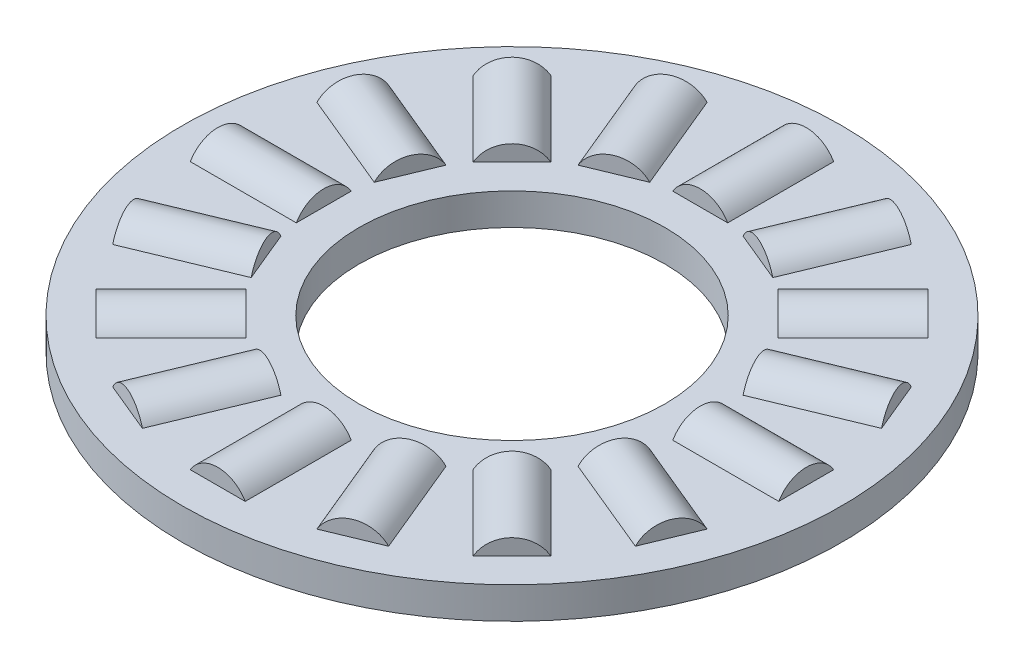
SolidWorks part; units mm, degrees
material "Alloy Steel"
ref_plane "Front Plane" through (0, 0, 0) normal (0, 0, 1) x (1, 0, 0)
ref_plane "Top Plane" through (0, 0, 0) normal (0, 1, 0) x (1, 0, 0)
ref_plane "Right Plane" through (0, 0, 0) normal (1, 0, 0) x (0, 0, -1)
sketch "Sketch1" plane through (0, 0, 0) normal (1, 0, 0) x (0, 0, -1)
  line L0 (-10.3187, 0) -> (10.3188, 0) construction
  line L1 (0, -0.9922) -> (0, 0.9922) construction
  line L2 (-10.3187, 0.4961) -> (-4.7879, 0.4961)
  line L3 (-10.3187, 0.4961) -> (-10.3187, -0.4961)
  line L4 (-10.3187, -0.4961) -> (-4.7879, -0.4961)
  line L5 (-4.7879, 0.4961) -> (-4.7879, -0.4961)
  line L7 (-7.5533, 0.9922) -> (-7.5533, 0.4961) construction
  line L8 (-9.2126, 0.9922) -> (-5.8941, 0.9922) construction
  line L9 (-9.2126, 0.9922) -> (-9.2126, -0.9922) construction
  line L10 (-9.2126, -0.9922) -> (-5.8941, -0.9922) construction
  line L11 (-5.8941, 0.9922) -> (-5.8941, -0.9922) construction
  line L12 (10.3188, 0.9922) -> (10.3188, -0.9922) construction
  point P16 (-9.2126, 0)
  point P21 (10.3188, 0)
  dimension "OD" = 20.6375
  dimension "ID" = 9.5758
  dimension "Washer Thickness" = 0.9922
  dimension "D1" = 3.3185
  dimension "Thickness" = 1.9844
sketch "Sketch6" plane through (0, 0, 0) normal (0, 1, 0) x (1, 0, 0)
  circle A0 centre (0, 0) radius 10.3188 construction
  circle A1 centre (0, 0) radius 4.7879 construction
  circle A2 centre (0, 0) radius 4.7625 construction
  dimension "For Shaft Diameter" = 9.525
  dimension "OD" = 20.6375
  dimension "ID" = 9.5758
sketch "Sketch5" plane through (0, 0, 0) normal (1, 0, 0) x (0, 0, -1)
  line L1 (-10.3187, 0.4961) -> (-4.7879, 0.4961)
  line L2 (-10.3187, 0.4961) -> (-10.3187, -0.4961)
  line L3 (-10.3187, -0.4961) -> (-4.7879, -0.4961)
  line L4 (-4.7879, 0.4961) -> (-4.7879, -0.4961)
revolve "Revolve3" add sketch "Sketch5" angle 360 about L1
sketch "Sketch3" plane through (0, 0, 0) normal (1, 0, 0) x (0, 0, -1)
  line L0 (-9.2126, 0.9922) -> (-9.2126, -0.9922) construction
  line L1 (-9.2126, 0) -> (-5.8941, 0)
  line L2 (-9.2126, 0) -> (-9.2126, 0.9922)
  line L3 (-9.2126, 0.9922) -> (-5.8941, 0.9922)
  line L4 (-5.8941, 0) -> (-5.8941, 0.9922)
revolve "Cut-Revolve1" cut sketch "Sketch3" angle 360 about L1
sketch "Sketch2" plane through (0, 0, 0) normal (1, 0, 0) x (0, 0, -1)
  line L1 (-9.2126, 0) -> (-5.8941, 0)
  line L2 (-9.2126, 0) -> (-9.2126, 0.9922)
  line L3 (-9.2126, 0.9922) -> (-5.8941, 0.9922)
  line L4 (-5.8941, 0) -> (-5.8941, 0.9922)
revolve "Revolve2" add sketch "Sketch2" angle 360 about L1
ref_axis "Axis1" through (0, 0.9922, 0) along (0, -1, 0)
pattern_circular "CirPattern1" count 16 every 22.5 about axis through (0, 0.9922, 0) along (0, -1, 0) of bodies 187 411
pattern_circular "CirPattern2" count 16 every 22.5 about axis through (0, 0.9922, 0) along (0, -1, 0) of "Cut-Revolve1"
equation "\"Rollers@CirPattern1\"= \"OD@Sketch1\" * 20"
equation "\"Angle@CirPattern1\" = 360/\"Rollers@CirPattern1\""
equation "\"D1@CirPattern2\" = \"Rollers@CirPattern1\""
equation "\"D2@CirPattern2\" = \"Angle@CirPattern1\""
equation "\"D1@Sketch1\"=((\"OD@Sketch1\"-\"ID@Sketch1\")/2)*.6"
